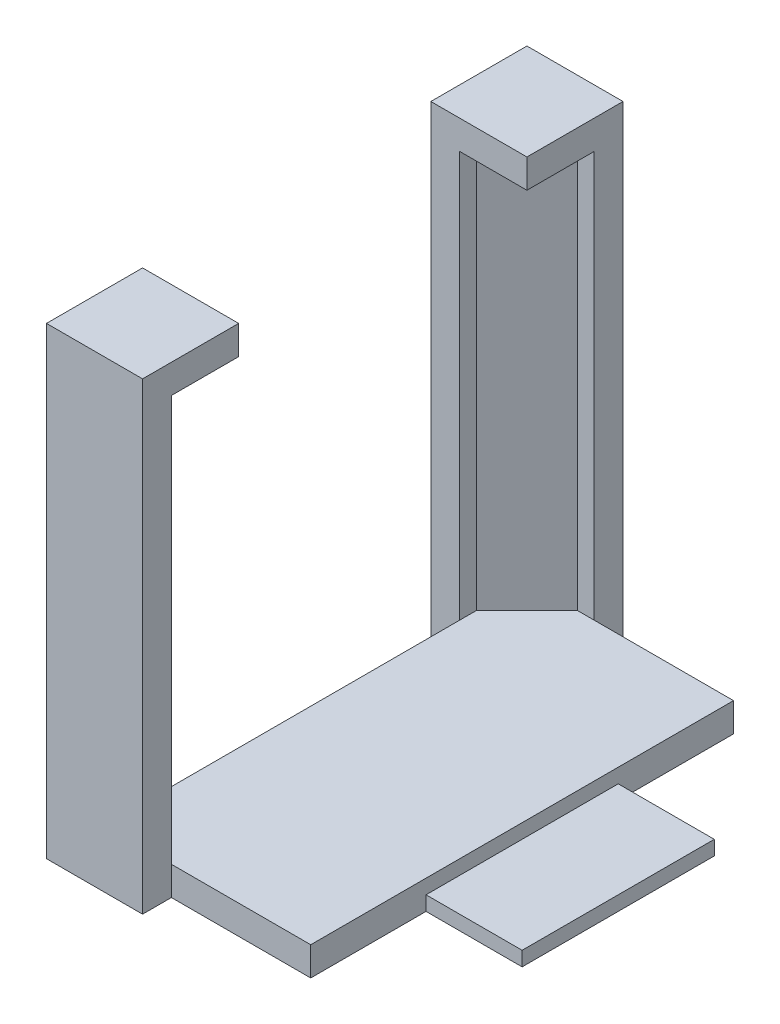
SolidWorks part; units mm, degrees
ref_plane "Front Plane" through (0, 0, 0) normal (0, 0, 1) x (1, 0, 0)
ref_plane "Top Plane" through (0, 0, 0) normal (0, 1, 0) x (1, 0, 0)
ref_plane "Right Plane" through (0, 0, 0) normal (1, 0, 0) x (0, 0, -1)
sketch "Sketch1" plane through (0, 0, 0) normal (0, 1, 0) x (1, 0, 0)
  line L0 (-21.5, 22) -> (0, 22) construction
  line L1 (0, 0) -> (-21.5, 0)
  line L2 (0, 0) -> (0, 44)
  line L3 (0, 44) -> (-21.5, 44)
  line L4 (-21.5, 0) -> (-21.5, 44)
  line L5 (-21.5, 37) -> (-24.5, 37)
  line L6 (-24.5, 37) -> (-24.5, 47)
  line L7 (-24.5, 47) -> (-14.5, 47)
  line L8 (-14.5, 47) -> (-14.5, 44)
  line L9 (-14.5, -3) -> (-14.5, 0)
  line L10 (-24.5, -3) -> (-14.5, -3)
  line L11 (-24.5, 7) -> (-24.5, -3)
  line L12 (-21.5, 7) -> (-24.5, 7)
  line L13 (0, 12) -> (10, 12)
  line L14 (10, 12) -> (10, 32)
  line L15 (10, 32) -> (0, 32)
  point P19 (10, 22)
  dimension "D1" = 44
  dimension "D2" = 21.5
  dimension "D3" = 3
  dimension "D4" = 10
  dimension "D5" = 20
  dimension "D6" = 10
  dimension "D7" = 10
extrude "Boss-Extrude1" add sketch "Sketch1" along normal blind 3 contours L4 L0 L2 L3 | L0 L4 L1 L2 region at (-10.75, 0, -33) region at (-10.75, 0, -11)
extrude "Boss-Extrude2" add sketch "Sketch1<3>" along normal blind 1.5 contours L14 L15 L2 L13 region at (5, 0, -22)
sketch "Sketch1<3>" plane through (0, 0, 0) normal (0, 1, 0) x (1, 0, 0) same geometry as "Sketch1"
extrude "Boss-Extrude3" add sketch "Sketch1<4>" along normal blind 45.25 contours L4 L12 L11 L10 L9 L1 | L8 L7 L6 L5 L4 L3 region at (-14.6414, 0, 1.5) region at (-23, 0, -37.1414)
sketch "Sketch1<4>" plane through (0, 0, 0) normal (0, 1, 0) x (1, 0, 0) same geometry as "Sketch1"
sketch "Sketch2" plane through (0, 45.25, 0) normal (0, 1, 0) x (1, 0, 0)
  line L0 (-21.5, 22) -> (0, 22) construction
  line L1 (-24.5, -3) -> (-14.5, -3)
  line L2 (-24.5, -3) -> (-24.5, 7)
  line L3 (-24.5, 7) -> (-14.5, 7)
  line L4 (-14.5, -3) -> (-14.5, 7)
  line L5 (-21.5, 7) -> (-21.5, 37) construction
  line L6 (0, 12) -> (0, 32) construction
  line L8 (-24.5, 47) -> (-24.5, 37)
  line L9 (-24.5, 47) -> (-14.5, 47)
  line L10 (-14.5, 47) -> (-14.5, 37)
  line L11 (-24.5, 37) -> (-14.5, 37)
extrude "Boss-Extrude4" add sketch "Sketch2" along normal blind 3
chamfer "Chamfer1" distance 5.25 angle 45 2 edges at (-21.5, 24.125, -44) (-21.5, 24.125, 0)
